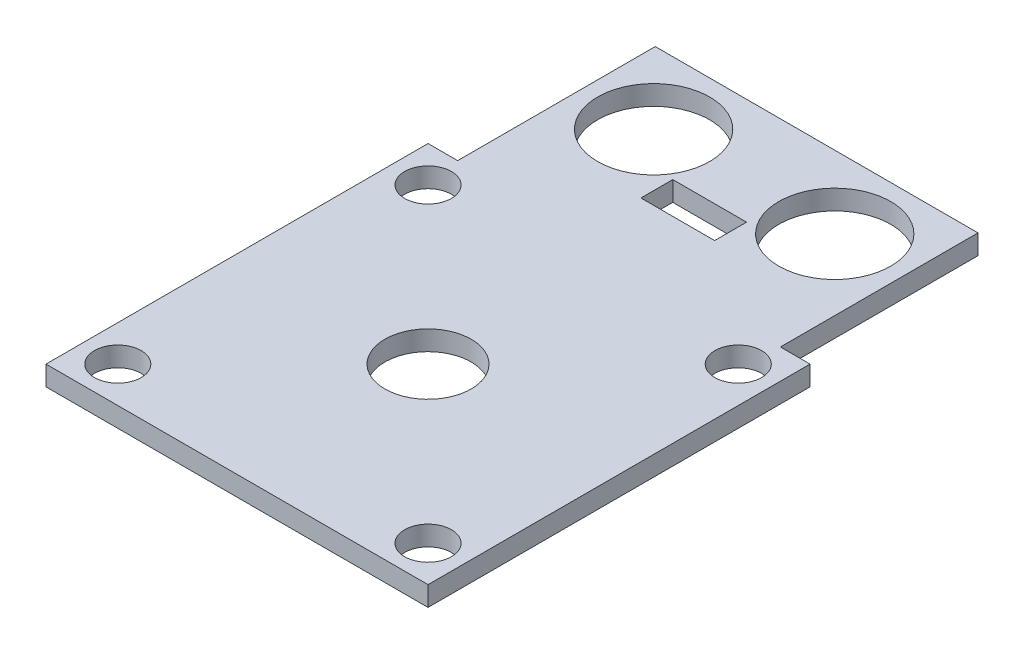
SolidWorks part; units mm, degrees
ref_plane "Front Plane" through (0, 0, 0) normal (0, 0, 1) x (1, 0, 0)
ref_plane "Top Plane" through (0, 0, 0) normal (0, 1, 0) x (1, 0, 0)
ref_plane "Right Plane" through (0, 0, 0) normal (1, 0, 0) x (0, 0, -1)
sketch "Sketch1" plane through (0, 0, 0) normal (0, 1, 0) x (1, 0, 0)
  circle A0 centre (0, 0) radius 20
  circle A1 centre (0, 0) radius 21
  dimension "D1" = 40
  dimension "D2" = 42
extrude "Boss-Extrude1" add sketch "Sketch1" along normal blind 3.5
ref_plane "Plane1" through (0, 3.5, 0) normal (0, 1, 0) x (1, 0, 0)
sketch "Sketch2" plane through (0, 3.5, 0) normal (0, 1, 0) x (1, 0, 0)
  line L0 (-23.55, 0) -> (23.55, 0) construction
  line L1 (-29, -29) -> (29, -29)
  line L2 (-29, -29) -> (-29, 29)
  line L3 (-29, 29) -> (29, 29)
  line L4 (29, -29) -> (29, 29)
  line L5 (-29, -29) -> (29, 29) construction
  line L6 (-29, 29) -> (29, -29) construction
  line L7 (-28.2, -28.2) -> (28.2, -28.2) construction
  line L8 (-28.2, -28.2) -> (-28.2, 28.2) construction
  line L9 (-28.2, 28.2) -> (28.2, 28.2) construction
  line L10 (28.2, -28.2) -> (28.2, 28.2) construction
  line L11 (-28.2, -28.2) -> (28.2, 28.2) construction
  line L12 (-28.2, 28.2) -> (28.2, -28.2) construction
  line L13 (-23.55, 28.2) -> (-23.55, 23.55) construction
  line L14 (-23.55, 23.55) -> (-28.2, 23.55) construction
  line L15 (0, 28.2) -> (0, -28.2) construction
  line L16 (0, 29) -> (0, 49) construction
  line L17 (-22.5, 49) -> (22.5, 49) construction
  line L18 (-22.5, 49) -> (-22.5, 29) construction
  line L19 (22.5, 49) -> (22.5, 29) construction
  line L20 (0, 49) -> (0, 48) construction
  line L21 (-4.9, 48) -> (4.9, 48) construction
  line L22 (-4.9, 48) -> (-4.9, 44.56) construction
  line L23 (-4.9, 44.56) -> (4.9, 44.56) construction
  line L24 (4.9, 44.56) -> (4.9, 48) construction
  line L25 (-24.5, 29) -> (-24.5, 51)
  line L26 (-24.5, 51) -> (24.5, 51)
  line L27 (24.5, 51) -> (24.5, 29)
  line L28 (-13.76, 39) -> (13.76, 39) construction
  line L29 (-5.6, 48.7) -> (5.6, 48.7)
  line L31 (5.6, 43.86) -> (-5.6, 43.86)
  line L32 (-5.6, 43.86) -> (-5.6, 48.7)
  line L33 (5.6, 43.86) -> (5.6, 48.7)
  line L34 (-24.5, 51) -> (-24.5, 59)
  line L35 (-24.5, 59) -> (24.5, 59)
  line L36 (24.5, 59) -> (24.5, 51)
  circle A0 centre (-23.55, 23.55) radius 2.55 construction
  circle A1 centre (23.55, 23.55) radius 2.55 construction
  circle A2 centre (23.55, -23.55) radius 2.55 construction
  circle A3 centre (-23.55, -23.55) radius 2.55 construction
  circle A4 centre (0, 0) radius 5.5563 construction
  circle A5 centre (13.76, 39) radius 7.5 construction
  circle A6 centre (-13.76, 39) radius 7.5 construction
  circle A7 centre (-13.76, 39) radius 8.5
  circle A8 centre (13.76, 39) radius 8.5
  circle A9 centre (0, 0) radius 6.55
  circle A10 centre (-23.55, 23.55) radius 3.55
  circle A11 centre (23.55, 23.55) radius 3.55
  circle A12 centre (23.55, -23.55) radius 3.55
  circle A13 centre (-23.55, -23.55) radius 3.55
  point P0 (0, 0)
  point P5 (0, 0)
  point P15 (0, 0)
  point P34 (0, 49)
  point P40 (0, 48)
  point P49 (0, 39)
  point P56 (0, 43.86)
  point P59 (0, 48.7)
  dimension "D4" = 5.1
  dimension "D5" = 11.1125
  dimension "D15" = 15
  dimension "D16" = 17
  dimension "D17" = 0.7
  dimension "D20" = 13.1
  dimension "D21" = 7.1
  dimension "D22" = 8
  dimension "D1" = 58
  dimension "D2" = 56.4
  dimension "D3" = 47.1
  dimension "D6" = 20
  dimension "D7" = 45
  dimension "D8" = 1
  dimension "D9" = 9.8
  dimension "D10" = 3.44
  dimension "D11" = 2
  dimension "D12" = 2
  dimension "D13" = 2
  dimension "D14" = 27.52
  dimension "D18" = 0.7
  dimension "D19" = 0.7
extrude "Boss-Extrude2" add sketch "Sketch2" along normal blind 3 contours L1 L4 L3 L2 A4 A1 A0 A2 A3 | L27 L26 L25 L3 A8 A7 L33 L31 L32 L29 region at (-28.1798, 3.5, 0) region at (0, 3.5, -40.1992)
sketch "Sketch3" plane through (0, 3.5, 0) normal (0, 1, 0) x (1, 0, 0)
  line L0 (-5.6, 48.7) -> (5.6, 48.7)
  line L1 (5.6, 48.7) -> (5.6, 43.86)
  line L2 (5.6, 43.86) -> (-5.6, 43.86)
  line L3 (-5.6, 43.86) -> (-5.6, 48.7)
  line L4 (-13.76, 47.5) -> (-13.76, 30.5) construction
  line L5 (13.76, 47.5) -> (13.76, 30.5) construction
  line L6 (-24.5, 29) -> (24.5, 29)
  line L7 (24.5, 29) -> (24.5, 51)
  line L8 (24.5, 51) -> (-24.5, 51)
  line L9 (-24.5, 51) -> (-24.5, 29)
  line L10 (-24.5, 51) -> (-24.5, 59)
  line L11 (-24.5, 59) -> (24.5, 59)
  line L12 (24.5, 59) -> (24.5, 51)
  circle A0 centre (-13.76, 39) radius 8.5 construction
  circle A1 centre (-13.76, 39) radius 8.5
  circle A2 centre (13.76, 39) radius 8.5 construction
  circle A3 centre (13.76, 39) radius 8.5
  dimension "D1" = 8
sketch "Sketch4" plane through (0, 3.5, 0) normal (0, 1, 0) x (1, 0, 0)
  line L4 (-5.6791, 42.84) -> (-5.6791, 38)
  line L5 (5.5209, 38) -> (5.5209, 42.84)
  line L10 (-24.5, 29) -> (-24.5, 37)
  line L11 (-24.5, 51) -> (-24.5, 29) construction
  line L12 (24.5, 29) -> (24.5, 37)
  line L13 (24.5, 29) -> (24.5, 51) construction
  line L14 (-24.5, 37) -> (-24.5, 59)
  line L15 (24.5, 37) -> (24.5, 59)
  line L16 (-24.5, 59) -> (24.5, 59)
  line L17 (-24.5, 37) -> (24.5, 37)
  line L18 (0, 59) -> (0, 37) construction
  line L23 (-5.6791, 38) -> (5.5209, 38)
  line L24 (5.5209, 42.84) -> (-5.6791, 42.84)
  line L25 (-5.6791, 58) -> (5.5209, 58) construction
  line L26 (5.5209, 58) -> (5.5209, 53.16) construction
  line L27 (5.5209, 53.16) -> (-5.6791, 53.16) construction
  line L28 (-5.6791, 53.16) -> (-5.6791, 58) construction
  line L29 (-13.75, 56.5) -> (-13.75, 39.5) construction
  line L30 (-13.75, 48) -> (13.75, 48) construction
  circle A4 centre (-13.75, 48) radius 8.5
  circle A5 centre (13.75, 48) radius 8.5
  point P53 (0, 48)
  dimension "D2" = 17
  dimension "D1" = 8
  dimension "D3" = 22
  dimension "D4" = 1
  dimension "D5" = 5.5209
  dimension "D6" = 11.2
  dimension "D7" = 4.84
  dimension "D8" = 27.5
extrude "Ignore" add sketch "Sketch3" along normal blind 3 contours L3 L2 L1 L0 | L12 L11 L10 L8 | A3 | A1 region at (0, 3.5, -46.28) region at (0, 3.5, -55) region at (-13.76, 3.5, -39) region at (13.76, 3.5, -39)
extrude "Cut-Extrude2" cut sketch "Sketch4" along normal through all contours A4 | A5 | L28 L27 L26 L25 | L5 L24 L4 L23 region at (-0.0791, 3.5, -40.42) region at (-13.75, 3.5, -48) region at (13.75, 3.5, -48)
